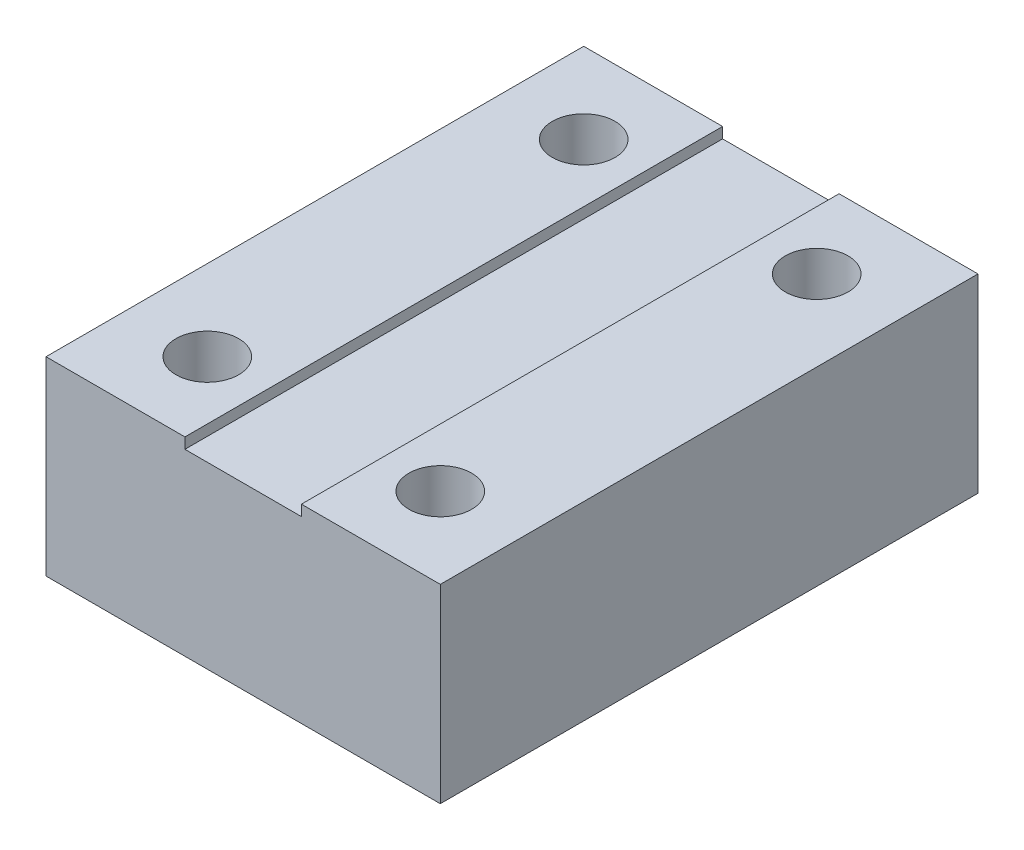
SolidWorks part; units mm, degrees
ref_plane "Piano frontale" through (0, 0, 0) normal (0, 0, 1) x (1, 0, 0)
ref_plane "Piano superiore" through (0, 0, 0) normal (0, 1, 0) x (1, 0, 0)
ref_plane "Piano destro" through (0, 0, 0) normal (1, 0, 0) x (0, 0, -1)
sketch "Schizzo1" plane through (0, 0, 0) normal (0, 0, 1) x (1, 0, 0)
  line L1 (-11, -5.3) -> (11, -5.3)
  line L2 (-11, -5.3) -> (-11, 5.3)
  line L3 (-11, 5.3) -> (11, 5.3)
  line L4 (11, -5.3) -> (11, 5.3)
  line L5 (-11, -5.3) -> (11, 5.3) construction
  line L6 (-11, 5.3) -> (11, -5.3) construction
  point P0 (0, 0)
  dimension "D1" = 22
  dimension "D2" = 10.6
extrude "Estrusione-Estrusione1" add sketch "Schizzo1" along normal mid plane 30
sketch "Schizzo5" plane through (0, 5.3, 0) normal (0, 1, 0) x (1, 0, 0)
  line L0 (11, -15) -> (11, 15) construction
  line L1 (-6.5, -10.5) -> (6.5, -10.5) construction
  line L2 (-6.5, -10.5) -> (-6.5, 10.5) construction
  line L3 (-6.5, 10.5) -> (6.5, 10.5) construction
  line L4 (6.5, -10.5) -> (6.5, 10.5) construction
  line L5 (-6.5, -10.5) -> (6.5, 10.5) construction
  line L6 (-6.5, 10.5) -> (6.5, -10.5) construction
  line L7 (11, 15) -> (-11, 15) construction
  line L10 (3.25, -15) -> (-3.25, -15)
  line L11 (3.25, -15) -> (3.25, 15)
  line L12 (3.25, 15) -> (-3.25, 15)
  line L13 (-3.25, -15) -> (-3.25, 15)
  line L14 (3.25, -15) -> (-3.25, 15) construction
  line L15 (3.25, 15) -> (-3.25, -15) construction
  circle A0 centre (6.5, 10.5) radius 1.75
  circle A1 centre (6.5, -10.5) radius 1.75
  circle A2 centre (-6.5, -10.5) radius 1.75
  circle A3 centre (-6.5, 10.5) radius 1.75
  point P0 (0, 0)
  point P12 (0, 0)
  dimension "D3" = 3.5
  dimension "D1" = 4.5
  dimension "D2" = 6.5
  dimension "D4" = 4.5
extrude "Taglio-Estrusione3" cut sketch "Schizzo5" against normal up to next contours A3 | A2 | A1 | A0
extrude "Taglio-Estrusione4" cut sketch "Schizzo5<3>" against normal blind 0.6 contours L13 L12 L11 L10
sketch "Schizzo5<3>" plane through (0, 5.3, 0) normal (0, 1, 0) x (1, 0, 0) same geometry as "Schizzo5"
